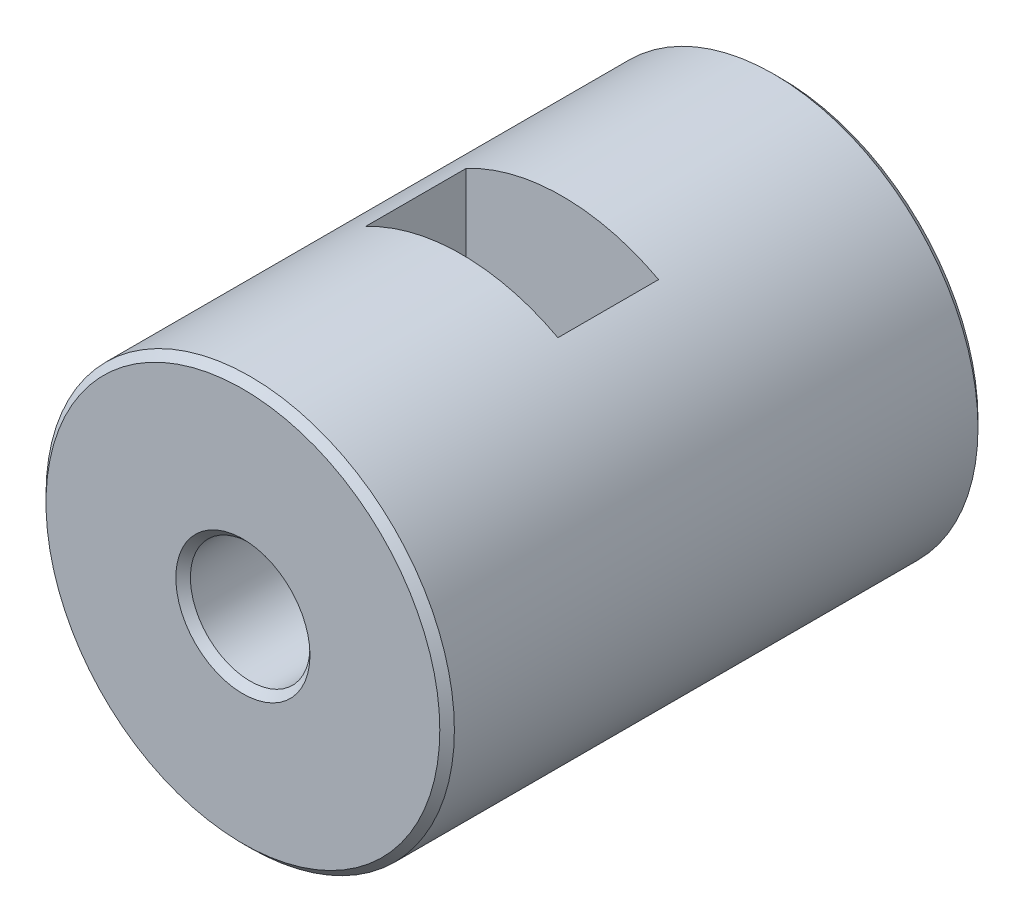
SolidWorks part; units mm, degrees
ref_plane "Front Plane" through (0, 0, 0) normal (0, 0, 1) x (1, 0, 0)
ref_plane "Top Plane" through (0, 0, 0) normal (0, 1, 0) x (1, 0, 0)
ref_plane "Right Plane" through (0, 0, 0) normal (1, 0, 0) x (0, 0, -1)
sketch "Sketch1" plane through (0, 0, 0) normal (0, 0, 1) x (1, 0, 0)
  circle A0 centre (0, 0) radius 14
  dimension "D1" = 28
extrude "Boss-Extrude1" add sketch "Sketch1" along normal blind 15
sketch "Sketch2" plane through (0, 0, 15) normal (0, 0, 1) x (1, 0, 0)
  line L0 (0, 14) -> (0, -14) construction
  line L1 (-6.6, 3.8105) -> (-6.6, 12.3467)
  line L3 (-6.6, 3.8105) -> (-6.6, -3.8105)
  line L4 (-6.6, -3.8105) -> (0, -7.621)
  line L5 (0, -7.621) -> (6.6, -3.8105)
  line L6 (6.6, -3.8105) -> (6.6, 3.695)
  line L8 (6.6, 3.695) -> (6.6, 12.3467)
  line L10 (6.3952, 3.9288) -> (3.1452, 5.8052) [skipped]
  line L11 (-3.3, 5.7158) -> (-6.55, 3.8394) [skipped]
  circle A0 centre (0, 0) radius 14 construction
  circle A1 centre (0, 0) radius 6.5 construction
  circle A3 centre (0, 0) radius 14
  arc A4 (-6.6, 12.3467) -> (6.6, 12.3467) centre (0, 0) ccw
  dimension "D1" = 13.2
  dimension "D2" = 0
extrude "Boss-Extrude2" add sketch "Sketch2" along normal blind 6.9
sketch "Sketch3" plane through (0, 0, 21.9) normal (0, 0, 1) x (1, 0, 0)
  arc A0 (6.6, 12.3467) -> (-6.6, 12.3467) centre (0, 0) ccw construction
  arc A1 (-6.6, 12.3467) -> (6.6, 12.3467) centre (0, 0) ccw construction
  arc A2 (6.6, 12.3467) -> (-6.6, 12.3467) centre (0, 0) ccw
  arc A3 (-6.6, 12.3467) -> (6.6, 12.3467) centre (0, 0) ccw
extrude "Boss-Extrude3" add sketch "Sketch3" along normal blind 15
sketch "Sketch4" plane through (0, 0, 36.9) normal (0, 0, 1) x (1, 0, 0)
  circle A0 centre (0, 0) radius 4.1
  dimension "D1" = 8.2
extrude "Cut-Extrude1" cut sketch "Sketch4" against normal through all
chamfer "Chamfer1" distance 0.5 angle 45 4 edges at (14, 0, 0) (4.1, 0, 0) (14, 0, 36.9) (4.1, 0, 36.9)
